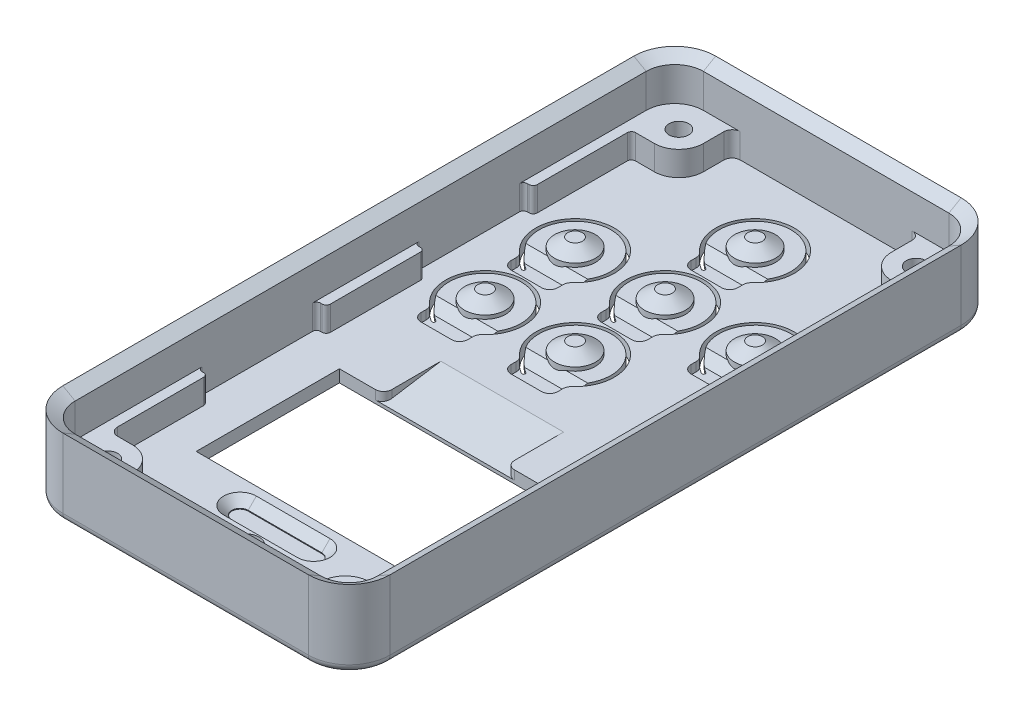
SolidWorks part; units mm, degrees
ref_plane "Front Plane" through (0, 0, 0) normal (0, 0, 1) x (1, 0, 0)
ref_plane "Top Plane" through (0, 0, 0) normal (0, 1, 0) x (1, 0, 0)
ref_plane "Right Plane" through (0, 0, 0) normal (1, 0, 0) x (0, 0, -1)
sketch "Base Sketch" plane through (0, 0, 0) normal (0, 1, 0) x (1, 0, 0)
  line L0 (0, 0) -> (40, 0)
  line L1 (40, 0) -> (40, 79.79)
  line L2 (40, 79.79) -> (0, 79.79)
  line L3 (0, 79.79) -> (0, 0)
extrude "Base" add sketch "Base Sketch" along normal blind 9.5
fillet "Corner Rounds R5" radius 5 4 edges at (0, 4.75, -79.79) (40, 4.75, -79.79) (40, 4.75, 0) (0, 4.75, 0)
shell "Shell 1.5" thickness 1.5 removed face at (20, 9.5, -39.895)
sketch "Boss Sketch" plane through (0, 0, 0) normal (0, 1, 0) x (1, 0, 0)
  line L0 (1.5, 1.5) -> (8.5, 1.5)
  line L1 (8.5, 1.5) -> (8.5, 5)
  line L2 (5.5, 8) -> (1.5, 8)
  line L3 (1.5, 8) -> (1.5, 1.5)
  line L4 (38.5, 1.5) -> (31.5, 1.5)
  line L5 (31.5, 1.5) -> (31.5, 5)
  line L6 (34.5, 8) -> (38.5, 8)
  line L7 (38.5, 8) -> (38.5, 1.5)
  line L16 (1.5, 78.29) -> (8.5, 78.29)
  line L17 (8.5, 78.29) -> (8.5, 74.79)
  line L18 (5.5, 71.79) -> (1.5, 71.79)
  line L19 (1.5, 71.79) -> (1.5, 78.29)
  line L20 (38.5, 78.29) -> (31.5, 78.29)
  line L21 (31.5, 78.29) -> (31.5, 74.79)
  line L22 (34.5, 71.79) -> (38.5, 71.79)
  line L23 (38.5, 71.79) -> (38.5, 78.29)
  arc A0 (8.5, 5) -> (5.5, 8) centre (5.4999, 4.9999) ccw
  circle A1 centre (5.5, 5) radius 1
  arc A2 (31.5, 5) -> (34.5, 8) centre (34.5001, 4.9999) cw
  circle A3 centre (34.5, 5) radius 1
  circle A5 centre (5.5, 74.79) radius 1
  circle A7 centre (34.5, 74.79) radius 1
  arc A8 (8.5, 74.79) -> (5.5, 71.79) centre (5.4999, 74.7901) cw
  arc A9 (31.5, 74.79) -> (34.5, 71.79) centre (34.5001, 74.7901) ccw
extrude "Corner Bosses (stop at ledge y4.5) + M2 Holes" add sketch "Boss Sketch" along normal blind 4.5
sketch "Ledge Sketch" plane through (0, 0, 0) normal (0, 1, 0) x (1, 0, 0)
  line L0 (1.5, 8) -> (2.7, 8)
  line L1 (2.7, 8) -> (2.7, 20)
  line L2 (2.7, 20) -> (1.5, 20)
  line L3 (1.5, 20) -> (1.5, 8)
  line L4 (37.3, 8) -> (38.5, 8)
  line L5 (38.5, 8) -> (38.5, 20)
  line L6 (38.5, 20) -> (37.3, 20)
  line L7 (37.3, 20) -> (37.3, 8)
  line L8 (1.5, 34.5) -> (2.7, 34.5)
  line L9 (2.7, 34.5) -> (2.7, 46.5)
  line L10 (2.7, 46.5) -> (1.5, 46.5)
  line L11 (1.5, 46.5) -> (1.5, 34.5)
  line L12 (37.3, 34.5) -> (38.5, 34.5)
  line L13 (38.5, 34.5) -> (38.5, 46.5)
  line L14 (38.5, 46.5) -> (37.3, 46.5)
  line L15 (37.3, 46.5) -> (37.3, 34.5)
  line L16 (1.5, 59.79) -> (2.7, 59.79)
  line L17 (2.7, 59.79) -> (2.7, 71.79)
  line L18 (2.7, 71.79) -> (1.5, 71.79)
  line L19 (1.5, 71.79) -> (1.5, 59.79)
  line L20 (37.3, 59.79) -> (38.5, 59.79)
  line L21 (38.5, 59.79) -> (38.5, 71.79)
  line L22 (38.5, 71.79) -> (37.3, 71.79)
  line L23 (37.3, 71.79) -> (37.3, 59.79)
extrude "Side Ledges" add sketch "Ledge Sketch" along normal blind 4.5
fillet "Outer Face Round R1" radius 1 8 edges at (1.4645, 0, -1.4645) (20, 0, 0) (38.5355, 0, -1.4645) (40, 0, -39.895) (38.5355, 0, -78.3255) (20, 0, -79.79) (1.4645, 0, -78.3255) (0, 0, -39.895)
sketch "Window Sketch" plane through (0, 0, 0) normal (0, 1, 0) x (1, 0, 0)
  line L0 (7.1, 14.5) -> (32.9, 14.5)
  line L1 (32.9, 14.5) -> (32.9, 31.7)
  line L2 (32.9, 31.7) -> (7.1, 31.7)
  line L3 (7.1, 31.7) -> (7.1, 14.5)
extrude "Display Window" cut sketch "Window Sketch" along normal through all
ref_plane "Mid Plane X20" through (20, 0, 0) normal (1, 0, 0) x (0, 0, -1)
sketch "Ramp Sketch" plane through (20, 0, 0) normal (1, 0, 0) x (0, 0, -1)
  line L0 (31, 0.4) -> (31.7, 0.4)
  line L1 (31.7, 0.4) -> (38.7, 1.5)
  line L2 (38.7, 1.5) -> (38.7, 2.5)
  line L3 (38.7, 2.5) -> (31, 2.5)
  line L4 (31, 2.5) -> (31, 0.4)
extrude "Cable Ramp" cut sketch "Ramp Sketch" against normal blind 7.5 and the other way blind 7.5
ref_plane "Plate Inner Face" through (0, 1.5, 0) normal (0, 1, 0) x (1, 0, 0)
sketch "LED Window Sketch" plane through (0, 1.5, 0) normal (0, 1, 0) x (1, 0, 0)
  circle A0 centre (20, 7.28) radius 1.7
  dimension "D1" = 3.4
extrude "LED Window" cut sketch "LED Window Sketch" against normal blind 1.1
sketch "Plunger Stems Sketch" plane through (0, 1.5, 0) normal (0, 1, 0) x (1, 0, 0)
  circle A0 centre (9, 47.6) radius 2.5
  circle A1 centre (20, 47.6) radius 2.5
  circle A2 centre (9, 58.6) radius 2.5
  circle A3 centre (20, 58.6) radius 2.5
  circle A4 centre (31, 58.6) radius 2.5
  circle A5 centre (20, 69.6) radius 2.5
extrude "Plunger Stems 5.0" add sketch "Plunger Stems Sketch" along normal blind 0.45
ref_plane "Plunger Cone Base" through (0, 1.95, 0) normal (0, 1, 0) x (1, 0, 0)
sketch "Plunger Cone Sketch" plane through (0, 1.95, 0) normal (0, 1, 0) x (1, 0, 0)
  circle A0 centre (9, 47.6) radius 2.5
  circle A1 centre (20, 47.6) radius 2.5
  circle A2 centre (9, 58.6) radius 2.5
  circle A3 centre (20, 58.6) radius 2.5
  circle A4 centre (31, 58.6) radius 2.5
  circle A5 centre (20, 69.6) radius 2.5
extrude "Plunger Cones to 1.8" add sketch "Plunger Cone Sketch" along normal blind 1 draft 57.995
fillet "Boss Junction Fillets R1" radius 1 7 edges at (37.3, 3, -71.79) (37.3, 3, -8) (2.7, 3, -8) (31.5, 3, -78.29) (8.5, 3, -78.29) (31.5, 3, -1.5) (8.5, 3, -1.5)
sketch "C-Slot Sketch" plane through (0, 0, 0) normal (0, 1, 0) x (1, 0, 0)
  arc A0 (10.4434, 43.0222) -> (7.5566, 43.0222) centre (9, 47.6) ccw
  arc A1 (7.5566, 43.0222) -> (7.6769, 43.4036) centre (7.6168, 43.2129) ccw
  arc A2 (7.6769, 43.4036) -> (10.3231, 43.4036) centre (9, 47.6) cw
  arc A3 (10.3231, 43.4036) -> (10.4434, 43.0222) centre (10.3832, 43.2129) ccw
  arc A4 (21.4434, 43.0222) -> (18.5566, 43.0222) centre (20, 47.6) ccw
  arc A5 (18.5566, 43.0222) -> (18.6769, 43.4036) centre (18.6168, 43.2129) ccw
  arc A6 (18.6769, 43.4036) -> (21.3231, 43.4036) centre (20, 47.6) cw
  arc A7 (21.3231, 43.4036) -> (21.4434, 43.0222) centre (21.3832, 43.2129) ccw
  arc A8 (10.4434, 54.0222) -> (7.5566, 54.0222) centre (9, 58.6) ccw
  arc A9 (7.5566, 54.0222) -> (7.6769, 54.4036) centre (7.6168, 54.2129) ccw
  arc A10 (7.6769, 54.4036) -> (10.3231, 54.4036) centre (9, 58.6) cw
  arc A11 (10.3231, 54.4036) -> (10.4434, 54.0222) centre (10.3832, 54.2129) ccw
  arc A12 (21.4434, 54.0222) -> (18.5566, 54.0222) centre (20, 58.6) ccw
  arc A13 (18.5566, 54.0222) -> (18.6769, 54.4036) centre (18.6168, 54.2129) ccw
  arc A14 (18.6769, 54.4036) -> (21.3231, 54.4036) centre (20, 58.6) cw
  arc A15 (21.3231, 54.4036) -> (21.4434, 54.0222) centre (21.3832, 54.2129) ccw
  arc A16 (32.4434, 54.0222) -> (29.5566, 54.0222) centre (31, 58.6) ccw
  arc A17 (29.5566, 54.0222) -> (29.6769, 54.4036) centre (29.6168, 54.2129) ccw
  arc A18 (29.6769, 54.4036) -> (32.3231, 54.4036) centre (31, 58.6) cw
  arc A19 (32.3231, 54.4036) -> (32.4434, 54.0222) centre (32.3832, 54.2129) ccw
  arc A20 (21.4434, 65.0222) -> (18.5566, 65.0222) centre (20, 69.6) ccw
  arc A21 (18.5566, 65.0222) -> (18.6769, 65.4036) centre (18.6168, 65.2129) ccw
  arc A22 (18.6769, 65.4036) -> (21.3231, 65.4036) centre (20, 69.6) cw
  arc A23 (21.3231, 65.4036) -> (21.4434, 65.0222) centre (21.3832, 65.2129) ccw
sketch "Sketch10" plane through (0, 1.5, 0) normal (0, 1, 0) x (1, 0, 0)
  line L0 (11.864, 44.259) -> (11.864, 41.636)
  line L1 (11.864, 41.636) -> (6.136, 41.636)
  line L2 (6.136, 41.636) -> (6.136, 44.259)
  line L3 (6.136, 44.259) -> (11.864, 44.259)
  line L4 (22.864, 44.259) -> (22.864, 41.636)
  line L5 (22.864, 41.636) -> (17.136, 41.636)
  line L6 (17.136, 41.636) -> (17.136, 44.259)
  line L7 (17.136, 44.259) -> (22.864, 44.259)
  line L8 (11.864, 55.259) -> (11.864, 52.636)
  line L9 (11.864, 52.636) -> (6.136, 52.636)
  line L10 (6.136, 52.636) -> (6.136, 55.259)
  line L11 (6.136, 55.259) -> (11.864, 55.259)
  line L12 (22.864, 55.259) -> (22.864, 52.636)
  line L13 (22.864, 52.636) -> (17.136, 52.636)
  line L14 (17.136, 52.636) -> (17.136, 55.259)
  line L15 (17.136, 55.259) -> (22.864, 55.259)
  line L16 (33.864, 55.259) -> (33.864, 52.636)
  line L17 (33.864, 52.636) -> (28.136, 52.636)
  line L18 (28.136, 52.636) -> (28.136, 55.259)
  line L19 (28.136, 55.259) -> (33.864, 55.259)
  line L20 (22.864, 66.259) -> (22.864, 63.636)
  line L21 (22.864, 63.636) -> (17.136, 63.636)
  line L22 (17.136, 63.636) -> (17.136, 66.259)
  line L23 (17.136, 66.259) -> (22.864, 66.259)
extrude "Cut-Extrude7" cut sketch "Sketch10" against normal blind 1.1
sketch "Sketch11" plane through (0, 0, 0) normal (0, 1, 0) x (1, 0, 0)
  arc A0 (11.4, 43.4431) -> (6.6, 43.4431) centre (9, 47.6) ccw
  arc A1 (6.6, 43.4431) -> (6.8, 43.7895) centre (6.7, 43.6163) ccw
  arc A2 (6.8, 43.7895) -> (11.2, 43.7895) centre (9, 47.6) cw
  arc A3 (11.2, 43.7895) -> (11.4, 43.4431) centre (11.3, 43.6163) ccw
  arc A4 (22.4, 43.4431) -> (17.6, 43.4431) centre (20, 47.6) ccw
  arc A5 (17.6, 43.4431) -> (17.8, 43.7895) centre (17.7, 43.6163) ccw
  arc A6 (17.8, 43.7895) -> (22.2, 43.7895) centre (20, 47.6) cw
  arc A7 (22.2, 43.7895) -> (22.4, 43.4431) centre (22.3, 43.6163) ccw
  arc A8 (11.4, 54.4431) -> (6.6, 54.4431) centre (9, 58.6) ccw
  arc A9 (6.6, 54.4431) -> (6.8, 54.7895) centre (6.7, 54.6163) ccw
  arc A10 (6.8, 54.7895) -> (11.2, 54.7895) centre (9, 58.6) cw
  arc A11 (11.2, 54.7895) -> (11.4, 54.4431) centre (11.3, 54.6163) ccw
  arc A12 (22.4, 54.4431) -> (17.6, 54.4431) centre (20, 58.6) ccw
  arc A13 (17.6, 54.4431) -> (17.8, 54.7895) centre (17.7, 54.6163) ccw
  arc A14 (17.8, 54.7895) -> (22.2, 54.7895) centre (20, 58.6) cw
  arc A15 (22.2, 54.7895) -> (22.4, 54.4431) centre (22.3, 54.6163) ccw
  arc A16 (33.4, 54.4431) -> (28.6, 54.4431) centre (31, 58.6) ccw
  arc A17 (28.6, 54.4431) -> (28.8, 54.7895) centre (28.7, 54.6163) ccw
  arc A18 (28.8, 54.7895) -> (33.2, 54.7895) centre (31, 58.6) cw
  arc A19 (33.2, 54.7895) -> (33.4, 54.4431) centre (33.3, 54.6163) ccw
  arc A20 (22.4, 65.4431) -> (17.6, 65.4431) centre (20, 69.6) ccw
  arc A21 (17.6, 65.4431) -> (17.8, 65.7895) centre (17.7, 65.6163) ccw
  arc A22 (17.8, 65.7895) -> (22.2, 65.7895) centre (20, 69.6) cw
  arc A23 (22.2, 65.7895) -> (22.4, 65.4431) centre (22.3, 65.6163) ccw
extrude "Button C-Slots 300deg 0.4" cut sketch "Sketch11" along normal through all
chamfer "Chamfer1" distance 1.1 angle 45 6 edges at (9, 1.5, -44.259) (20, 1.5, -66.259) (31, 1.5, -55.259) (20, 1.5, -55.259) (9, 1.5, -55.259) (20, 1.5, -44.259)
fillet "Fillet1" radius 1 24 edges at (11.864, 0.95, -43.7481) (11.864, 0.95, -41.636) (6.136, 0.95, -41.636) (6.136, 0.95, -43.7481) (22.864, 0.95, -63.636) (22.864, 0.95, -65.7481) (17.136, 0.95, -63.636) (17.136, 0.95, -65.7481) (33.864, 0.95, -52.636) (33.864, 0.95, -54.7481) (28.136, 0.95, -52.636) (28.136, 0.95, -54.7481) (22.864, 0.95, -52.636) (22.864, 0.95, -54.7481) (17.136, 0.95, -52.636) (17.136, 0.95, -54.7481) (11.864, 0.95, -52.636) (11.864, 0.95, -54.7481) (6.136, 0.95, -52.636) (6.136, 0.95, -54.7481) (22.864, 0.95, -41.636) (22.864, 0.95, -43.7481) (17.136, 0.95, -41.636) (17.136, 0.95, -43.7481)
fillet "Fillet2" radius 0.5 17 edges at (2.7, 3, -71.79) (1.5, 3, -59.79) (2.7, 3, -59.79) (38.5, 3, -59.79) (37.3, 3, -59.79) (38.5, 3, -46.5) (37.3, 3, -46.5) (2.7, 3, -46.5) (1.5, 3, -46.5) (38.5, 3, -34.5) (37.3, 3, -34.5) (2.7, 3, -34.5) (1.5, 3, -34.5) (38.5, 3, -20) (37.3, 3, -20) (2.7, 3, -20) (1.5, 3, -20)
fillet "Fillet3" radius 1 2 edges at (27.5, 0.95, -31.7) (12.5, 0.95, -31.7)
sketch "Button Symbols Cut Sketch" plane through (0, 0, 0) normal (0, 1, 0) x (1, 0, 0)
  line L0 (7.0908, 45.6908) -> (7.7272, 46.3272)
  line L1 (10.2728, 46.3272) -> (10.9092, 45.6908)
  line L2 (8.55, 47.2) -> (9.45, 47.2)
  line L3 (9.45, 47.2) -> (9.45, 44.4)
  line L4 (9.45, 44.4) -> (8.55, 44.4)
  line L5 (8.55, 44.4) -> (8.55, 47.2)
  line L6 (20, 44.8) -> (22.4249, 49)
  line L7 (22.4249, 49) -> (17.5751, 49)
  line L8 (17.5751, 49) -> (20, 44.8)
  line L9 (6.2, 58.6) -> (10.4, 56.1751)
  line L10 (10.4, 56.1751) -> (10.4, 61.0249)
  line L11 (10.4, 61.0249) -> (6.2, 58.6)
  line L12 (33.8, 58.6) -> (29.6, 61.0249)
  line L13 (29.6, 61.0249) -> (29.6, 56.1751)
  line L14 (29.6, 56.1751) -> (33.8, 58.6)
  line L15 (20, 72.4) -> (17.5751, 68.2)
  line L16 (17.5751, 68.2) -> (22.4249, 68.2)
  line L17 (22.4249, 68.2) -> (20, 72.4)
  arc A0 (10.9092, 45.6908) -> (7.0908, 45.6908) centre (9, 47.6) ccw
  arc A1 (7.7272, 46.3272) -> (10.2728, 46.3272) centre (9, 47.6) cw
  circle A2 centre (20, 58.6) radius 2.4
  circle A3 centre (20, 58.6) radius 1.5
sketch "Button Symbols Inlay Sketch" plane through (0, 0, 0) normal (0, 1, 0) x (1, 0, 0)
  line L0 (7.0908, 45.6908) -> (7.7272, 46.3272)
  line L1 (10.2728, 46.3272) -> (10.9092, 45.6908)
  line L2 (8.55, 47.2) -> (9.45, 47.2)
  line L3 (9.45, 47.2) -> (9.45, 44.4)
  line L4 (9.45, 44.4) -> (8.55, 44.4)
  line L5 (8.55, 44.4) -> (8.55, 47.2)
  line L6 (20, 44.8) -> (22.4249, 49)
  line L7 (22.4249, 49) -> (17.5751, 49)
  line L8 (17.5751, 49) -> (20, 44.8)
  line L9 (6.2, 58.6) -> (10.4, 56.1751)
  line L10 (10.4, 56.1751) -> (10.4, 61.0249)
  line L11 (10.4, 61.0249) -> (6.2, 58.6)
  line L12 (33.8, 58.6) -> (29.6, 61.0249)
  line L13 (29.6, 61.0249) -> (29.6, 56.1751)
  line L14 (29.6, 56.1751) -> (33.8, 58.6)
  line L15 (20, 72.4) -> (17.5751, 68.2)
  line L16 (17.5751, 68.2) -> (22.4249, 68.2)
  line L17 (22.4249, 68.2) -> (20, 72.4)
  arc A0 (10.9092, 45.6908) -> (7.0908, 45.6908) centre (9, 47.6) ccw
  arc A1 (7.7272, 46.3272) -> (10.2728, 46.3272) centre (9, 47.6) cw
  circle A2 centre (20, 58.6) radius 2.4
  circle A3 centre (20, 58.6) radius 1.5
sketch "Sketch14" plane through (0, 0, 0) normal (0, 1, 0) x (1, 0, 0)
  line L0 (8.4, 47) -> (8.4, 45.2)
  line L1 (9.6, 45.2) -> (9.6, 47)
  line L2 (20.5196, 44.9) -> (22.7713, 48.8)
  line L3 (22.2517, 49.7) -> (17.7483, 49.7)
  line L4 (17.2287, 48.8) -> (19.4804, 44.9)
  line L5 (6.1, 58.0804) -> (10, 55.8287)
  line L6 (10.9, 56.3483) -> (10.9, 60.8517)
  line L7 (10, 61.3713) -> (6.1, 59.1196)
  line L8 (33.9, 59.1196) -> (30, 61.3713)
  line L9 (29.1, 60.8517) -> (29.1, 56.3483)
  line L10 (30, 55.8287) -> (33.9, 58.0804)
  line L11 (19.4804, 72.5) -> (17.2287, 68.6)
  line L12 (17.7483, 67.7) -> (22.2517, 67.7)
  line L13 (22.7713, 68.6) -> (20.5196, 72.5)
  arc A0 (11.4513, 45.5431) -> (6.5487, 45.5431) centre (9, 47.6) ccw
  arc A1 (6.5487, 45.5431) -> (7.4679, 46.3144) centre (7.0083, 45.9288) ccw
  arc A2 (7.4679, 46.3144) -> (10.5321, 46.3144) centre (9, 47.6) cw
  arc A3 (10.5321, 46.3144) -> (11.4513, 45.5431) centre (10.9917, 45.9288) ccw
  arc A4 (8.4, 45.2) -> (9.6, 45.2) centre (9, 45.2) ccw
  arc A5 (9.6, 47) -> (8.4, 47) centre (9, 47) ccw
  arc A6 (19.4804, 44.9) -> (20.5196, 44.9) centre (20, 45.2) ccw
  arc A7 (22.7713, 48.8) -> (22.2517, 49.7) centre (22.2517, 49.1) ccw
  arc A8 (17.7483, 49.7) -> (17.2287, 48.8) centre (17.7483, 49.1) ccw
  arc A9 (6.1, 59.1196) -> (6.1, 58.0804) centre (6.4, 58.6) ccw
  arc A10 (10, 55.8287) -> (10.9, 56.3483) centre (10.3, 56.3483) ccw
  arc A11 (10.9, 60.8517) -> (10, 61.3713) centre (10.3, 60.8517) ccw
  circle A12 centre (20, 58.6) radius 3.1
  circle A13 centre (20, 58.6) radius 1.9
  arc A14 (33.9, 58.0804) -> (33.9, 59.1196) centre (33.6, 58.6) ccw
  arc A15 (30, 61.3713) -> (29.1, 60.8517) centre (29.7, 60.8517) ccw
  arc A16 (29.1, 56.3483) -> (30, 55.8287) centre (29.7, 56.3483) ccw
  arc A17 (20.5196, 72.5) -> (19.4804, 72.5) centre (20, 72.2) ccw
  arc A18 (17.2287, 68.6) -> (17.7483, 67.7) centre (17.7483, 68.3) ccw
  arc A19 (22.2517, 67.7) -> (22.7713, 68.6) centre (22.2517, 68.3) ccw
extrude "Button Symbol Recess 0.4" cut sketch "Sketch14" along normal blind 0.4
sketch "Sketch15" plane through (0, 0, 0) normal (0, 1, 0) x (1, 0, 0)
  line L0 (8.4, 47) -> (8.4, 45.2)
  line L1 (9.6, 45.2) -> (9.6, 47)
  line L2 (20.5196, 44.9) -> (22.7713, 48.8)
  line L3 (22.2517, 49.7) -> (17.7483, 49.7)
  line L4 (17.2287, 48.8) -> (19.4804, 44.9)
  line L5 (6.1, 58.0804) -> (10, 55.8287)
  line L6 (10.9, 56.3483) -> (10.9, 60.8517)
  line L7 (10, 61.3713) -> (6.1, 59.1196)
  line L8 (33.9, 59.1196) -> (30, 61.3713)
  line L9 (29.1, 60.8517) -> (29.1, 56.3483)
  line L10 (30, 55.8287) -> (33.9, 58.0804)
  line L11 (19.4804, 72.5) -> (17.2287, 68.6)
  line L12 (17.7483, 67.7) -> (22.2517, 67.7)
  line L13 (22.7713, 68.6) -> (20.5196, 72.5)
  arc A0 (11.4513, 45.5431) -> (6.5487, 45.5431) centre (9, 47.6) ccw
  arc A1 (6.5487, 45.5431) -> (7.4679, 46.3144) centre (7.0083, 45.9288) ccw
  arc A2 (7.4679, 46.3144) -> (10.5321, 46.3144) centre (9, 47.6) cw
  arc A3 (10.5321, 46.3144) -> (11.4513, 45.5431) centre (10.9917, 45.9288) ccw
  arc A4 (8.4, 45.2) -> (9.6, 45.2) centre (9, 45.2) ccw
  arc A5 (9.6, 47) -> (8.4, 47) centre (9, 47) ccw
  arc A6 (19.4804, 44.9) -> (20.5196, 44.9) centre (20, 45.2) ccw
  arc A7 (22.7713, 48.8) -> (22.2517, 49.7) centre (22.2517, 49.1) ccw
  arc A8 (17.7483, 49.7) -> (17.2287, 48.8) centre (17.7483, 49.1) ccw
  arc A9 (6.1, 59.1196) -> (6.1, 58.0804) centre (6.4, 58.6) ccw
  arc A10 (10, 55.8287) -> (10.9, 56.3483) centre (10.3, 56.3483) ccw
  arc A11 (10.9, 60.8517) -> (10, 61.3713) centre (10.3, 60.8517) ccw
  circle A12 centre (20, 58.6) radius 3.1
  circle A13 centre (20, 58.6) radius 1.9
  arc A14 (33.9, 58.0804) -> (33.9, 59.1196) centre (33.6, 58.6) ccw
  arc A15 (30, 61.3713) -> (29.1, 60.8517) centre (29.7, 60.8517) ccw
  arc A16 (29.1, 56.3483) -> (30, 55.8287) centre (29.7, 56.3483) ccw
  arc A17 (20.5196, 72.5) -> (19.4804, 72.5) centre (20, 72.2) ccw
  arc A18 (17.2287, 68.6) -> (17.7483, 67.7) centre (17.7483, 68.3) ccw
  arc A19 (22.2517, 67.7) -> (22.7713, 68.6) centre (22.2517, 68.3) ccw
extrude "Button Symbol Inlays 0.4 (colour 2)" add sketch "Sketch15" along normal blind 0.4 separate body
sketch "I2C Header Pocket Sketch" plane through (0, 1.5, 0) normal (0, 1, 0) x (1, 0, 0)
  line L0 (15.5, 9.4) -> (24.5, 9.4)
  line L1 (25.5, 10.4) -> (25.5, 11.9)
  line L2 (24.5, 12.9) -> (15.5, 12.9)
  line L3 (14.5, 11.9) -> (14.5, 10.4)
  line L4 (32.9, 14.5) -> (7.1, 14.5) construction
  arc A0 (24.5, 9.4) -> (25.5, 10.4) centre (24.5, 10.4) ccw
  arc A1 (25.5, 11.9) -> (24.5, 12.9) centre (24.5, 11.9) ccw
  arc A2 (15.5, 12.9) -> (14.5, 11.9) centre (15.5, 11.9) ccw
  arc A3 (14.5, 10.4) -> (15.5, 9.4) centre (15.5, 10.4) ccw
  dimension "D3" = 1
  dimension "D1" = 1.6
  dimension "D2" = 11
  dimension "D4" = 2.6
sketch "Sketch17" plane through (0, 1.5, 0) normal (0, 1, 0) x (1, 0, 0)
  line L0 (15.2, 10.45) -> (24.8, 10.45)
  line L1 (24.8, 11.85) -> (15.2, 11.85)
  arc A0 (24.8, 10.45) -> (24.8, 11.85) centre (24.8, 11.15) ccw
  arc A1 (15.2, 11.85) -> (15.2, 10.45) centre (15.2, 11.15) ccw
sketch "Sketch18" plane through (0, 0, -14.5) normal (0, 0, -1) x (-1, 0, 0)
  line L4 (-32.9, 1.5) -> (-32.9, 0)
  line L5 (-32.9, 0) -> (-7.1, 0)
  line L6 (-7.1, 0) -> (-7.1, 1.5)
  line L7 (-7.1, 1.5) -> (-32.9, 1.5)
  line L8 (-32.9, 1.5) -> (-32.9, 0)
  line L9 (-32.9, 0) -> (-7.1, 0)
  line L10 (-7.1, 0) -> (-7.1, 1.5)
  line L11 (-7.1, 1.5) -> (-32.9, 1.5)
  dimension "D1" = 0
extrude "Cut-Extrude16" cut sketch "Sketch18" against normal blind 0.3
sketch "Sketch19" plane through (0, 1.5, 0) normal (0, 1, 0) x (1, 0, 0)
  line L0 (15.2999, 10.35) -> (24.7001, 10.35)
  line L1 (25.5, 11.1499) -> (25.5, 11.1501)
  line L2 (24.7001, 11.95) -> (15.2999, 11.95)
  line L3 (14.5, 11.1501) -> (14.5, 11.1499)
  arc A0 (24.7001, 10.35) -> (25.5, 11.1499) centre (24.7001, 11.1499) ccw
  arc A1 (25.5, 11.1501) -> (24.7001, 11.95) centre (24.7001, 11.1501) ccw
  arc A2 (15.2999, 11.95) -> (14.5, 11.1501) centre (15.2999, 11.1501) ccw
  arc A3 (14.5, 11.1499) -> (15.2999, 10.35) centre (15.2999, 11.1499) ccw
sketch "Sketch20" plane through (0, 1.5, 0) normal (0, 1, 0) x (1, 0, 0)
  line L0 (15.5, 10.15) -> (24.5, 10.15)
  line L1 (24.5, 12.15) -> (15.5, 12.15)
  arc A0 (24.5, 10.15) -> (24.5, 12.15) centre (24.5, 11.15) ccw
  arc A1 (15.5, 12.15) -> (15.5, 10.15) centre (15.5, 11.15) ccw
extrude "I2C Header Lead Pocket 2.0 (0.2 skin)" cut sketch "Sketch20" against normal blind 1.1
chamfer "Chamfer3" distance 1 angle 45 4 edges at (20, 1.5, -12.15) (14.5, 1.5, -11.15) (25.5, 1.5, -11.15) (20, 1.5, -10.15)
sketch "Sketch21" plane through (0, 0, 0) normal (0, -1, 0) x (1, 0, 0)
  circle A0 centre (20, -7.28) radius 2.5
  circle A1 centre (20, -7.28) radius 1.7
  circle A2 centre (20, -7.28) radius 1.7 construction
  circle A3 centre (20, -7.28) radius 2.6
  dimension "D2" = 5
  dimension "D3" = 0.1
  dimension "D1" = 0
extrude "Cut-Extrude17" cut sketch "Sketch21" against normal blind 0.1
sketch "M2 Clearance 2.4 (screw from front) Sketch" plane through (0, 0, 0) normal (0, 1, 0) x (1, 0, 0)
  circle A0 centre (5.5, 5) radius 1.2
  circle A1 centre (34.5, 5) radius 1.2
  circle A2 centre (5.5, 74.79) radius 1.2
  circle A3 centre (34.5, 74.79) radius 1.2
extrude "M2 Clearance 2.4 (screw from front)" cut sketch "M2 Clearance 2.4 (screw from front) Sketch" along normal through all
ref_plane "Joint Bevel Plane" through (0, 8.5762, 0) normal (0, 1, 0) x (1, 0, 0)
sketch "Wall Bevel 30deg (joint) Sketch" plane through (0, 8.5762, 0) normal (0, 1, 0) x (1, 0, 0)
  line L0 (5, 1.6) -> (35, 1.6)
  line L1 (38.4, 5) -> (38.4, 74.79)
  line L2 (35, 78.19) -> (5, 78.19)
  line L3 (1.6, 74.79) -> (1.6, 5)
  arc A0 (35, 1.6) -> (38.4, 5) centre (35, 5) ccw
  arc A1 (38.4, 74.79) -> (35, 78.19) centre (35, 74.79) ccw
  arc A2 (5, 78.19) -> (1.6, 74.79) centre (5, 74.79) ccw
  arc A3 (1.6, 5) -> (5, 1.6) centre (5, 5) ccw
extrude "Wall Bevel 30deg (joint)" cut sketch "Wall Bevel 30deg (joint) Sketch" along normal blind 0.9238 draft 60 draft outward yes
sketch "M2 Head Counterbore 4.4 x 2.0 Sketch" plane through (0, 0, 0) normal (0, 1, 0) x (1, 0, 0)
  circle A0 centre (5.5, 5) radius 2.2
  circle A1 centre (34.5, 5) radius 2.2
  circle A2 centre (5.5, 74.79) radius 2.2
  circle A3 centre (34.5, 74.79) radius 2.2
extrude "M2 Head Counterbore 4.4 x 2.0" cut sketch "M2 Head Counterbore 4.4 x 2.0 Sketch" along normal blind 2
chamfer "M2 CSK Seats (head 1 mm below face)" distance 1 angle 45 4 edges at (34.5, 2, -72.59) (5.5, 2, -72.59) (34.5, 2, -2.8) (5.5, 2, -2.8)
